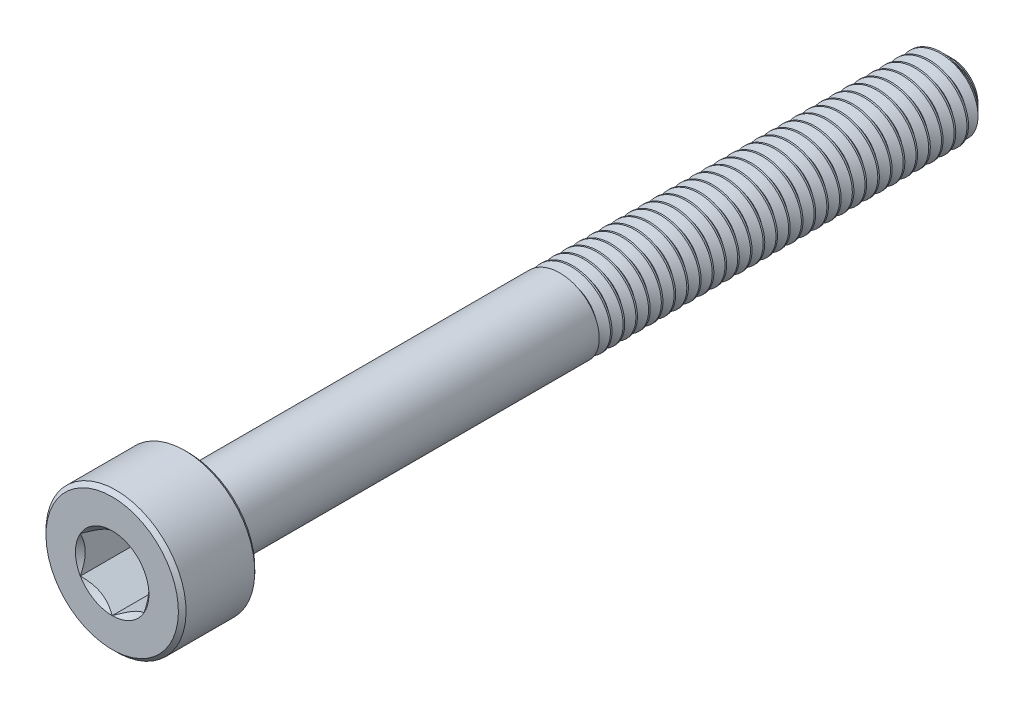
SolidWorks part; units mm, degrees
ref_plane "Front Plane" through (0, 0, 0) normal (0, 0, 1) x (1, 0, 0)
ref_plane "Top Plane" through (0, 0, 0) normal (0, 1, 0) x (1, 0, 0)
ref_plane "Right Plane" through (0, 0, 0) normal (1, 0, 0) x (0, 0, -1)
sketch "Sketch1" plane through (0, 0, 0) normal (1, 0, 0) x (0, 0, -1)
  line L0 (-16.5, 0) -> (16.5, 0) construction
  line L1 (16.5, 0) -> (16.5, 1) construction
  line L2 (16.5, 1) -> (16, 1.5) construction
  line L3 (16, 1.5) -> (16.125, 1.5) construction
  line L4 (16.125, 1.5) -> (-13.5, 1.5) construction
  line L5 (-13.5, 1.5) -> (-13.5, 2.75) construction
  line L6 (-13.5, 2.75) -> (-16.5, 2.75) construction
  line L7 (-16.5, 2.75) -> (-16.5, 0) construction
  line L8 (16.5, 1) -> (16.5, 1.5) construction
  line L9 (16.4687, 1.5541) -> (16.7187, 1.1211) construction
  line L10 (16.7187, 1.1211) -> (16.9687, 1.5541) construction
  line L11 (16.9687, 1.5541) -> (16.4687, 1.5541) construction
  line L12 (16.7187, 1.5541) -> (16.7187, 1.5) construction
  line L13 (16.7187, 1.1211) -> (16.7187, 1.1752) construction
  line L14 (16.6875, 1.1752) -> (16.75, 1.1752) construction
  line L15 (16.5, 1.5) -> (16.9375, 1.5) construction
  line L16 (16.4844, 1.5271) -> (16.9531, 1.5271) construction
  line L17 (16.5, 0) -> (16.5, -1.5) construction
  line L18 (-13.65, 2.75) -> (-13.5, 2.6) construction
  line L19 (-16.35, 2.75) -> (-16.5, 2.6) construction
  line L20 (-13.5, 1.5) -> (-13.5, 0) construction
  line L21 (-13.5, 0.75) -> (-3.5, 0.75) construction
  line L22 (-3.5, 0.75) -> (6.5, 0.75) construction
  line L23 (6.5, 0.75) -> (16.5, 0.75) construction
  line L24 (-3.5, 0.75) -> (-3.5, 1.5) construction
  line L25 (-3.5, 1.5) -> (-3.5, 2.75) construction
  line L26 (6.5, 0.75) -> (6.5, 2.75) construction
  point P0 (-16.5, 1.25)
  point P3 (15.25, 1.5)
  point P4 (0, 0)
  point P18 (6.5, 1.5)
  point P22 (16.7187, 1.1752)
  point P24 (16.125, 1.5)
  point P25 (16.7187, 1.5)
  point P28 (16.7187, 1.5271)
  point P29 (15.25, -1.5)
  point P30 (-3.5, 1.5)
  point P31 (-15, 2.75)
  point P37 (-14.025, 2.75)
  point P38 (-16.275, 2.75)
  point P45 (-3.5, 0.75)
  point P46 (6.5, 0.75)
  dimension "D1" = 45
  dimension "D2" = 0.0625
  dimension "D3" = 0.5
  dimension "D7" = 0.15
  dimension "D8" = 0.15
  dimension "D9" = 0.15
  dimension "D10" = 0.075
  dimension "D11" = 0.375
  dimension "Drive Size" = 2.5
  dimension "Head Diameter" = 5.5
  dimension "Head Height" = 3
  dimension "Thread Pitch" = 0.5
  dimension "Thread Major Diameter" = 3
  dimension "Length" = 30
  dimension "D12" = 0.375
  dimension "D4" = 1.25
sketch "Sketch2" plane through (0, 0, 0) normal (1, 0, 0) x (0, 0, -1)
  line L0 (-16.5, 0) -> (-16.5, 2.6)
  line L1 (-16.35, 2.75) -> (-13.65, 2.75)
  line L2 (-13.5, 2.6) -> (-13.5, 1.5)
  line L3 (-13.5, 1.5) -> (16, 1.5)
  line L4 (16, 1.5) -> (16.5, 1)
  line L5 (16.5, 1) -> (16.5, 0)
  line L6 (-13.65, 2.75) -> (-13.5, 2.6) construction
  line L7 (16.5, 0) -> (-16.5, 0)
  line L8 (-16.35, 2.75) -> (-16.5, 2.6) construction
  line L9 (-13.65, 2.75) -> (-13.5, 2.6)
  line L10 (-16.35, 2.75) -> (-16.5, 2.6)
revolve "Revolve1" add sketch "Sketch2" angle 360 about L7
sketch "Sketch3" plane through (0, 0, 16.5) normal (0, 0, 1) x (1, 0, 0)
  line L1 (1.25, -0.7217) -> (1.25, 0.7217)
  line L2 (1.25, 0.7217) -> (0, 1.4434)
  line L3 (0, 1.4434) -> (-1.25, 0.7217)
  line L4 (-1.25, 0.7217) -> (-1.25, -0.7217)
  line L5 (-1.25, -0.7217) -> (0, -1.4434)
  line L6 (0, -1.4434) -> (1.25, -0.7217)
  circle A0 centre (0, 0) radius 1.25 construction
extrude "Cut-Extrude1" cut sketch "Sketch3" against normal offset from surface (2 mm away) 1 up to face at (0, 2.6, 13.5)
sketch "Sketch4" plane through (0, 0, 16.5) normal (0, 0, 1) x (1, 0, 0)
  circle A0 centre (0, 0) radius 1.4434
extrude "Cut-Extrude2" cut sketch "Sketch4" against normal up to vertex (1.5 mm away) draft 45 up to point (0, 2.75, 15)
ref_plane "Plane1" through (0, 0, -16.125) normal (0, 0, 1) x (1, 0, 0)
split "Split1" bodies to split 106 resulting bodies 107 108 split by face at (0, 2.6, 13.5)
sketch "Sketch6" plane through (0, 0, -16.5) normal (0, 0, -1) x (-1, 0, 0)
  circle A0 centre (0, 0) radius 1.5
curve "Helix/Spiral1" pitch 0.5 height 15.575 radius 1.5 centre (0, 0, -16.5) axis (0, 0, 1) start towards (0, 1, 0)
sketch "Sketch7" plane through (0, 0, 0) normal (1, 0, 0) x (0, 0, -1)
  line L0 (16.4844, 1.5271) -> (16.9531, 1.5271)
  line L1 (16.9531, 1.5271) -> (16.75, 1.1752)
  line L2 (16.75, 1.1752) -> (16.6875, 1.1752)
  line L3 (16.6875, 1.1752) -> (16.4844, 1.5271)
sweep "Cut-Sweep1" cut profiles "Sketch7" path "Helix/Spiral1" align with end faces yes
sketch "Sketch8" plane through (0, 0, 13.5) normal (0, 0, -1) x (-1, 0, 0)
  circle A0 centre (0, 0) radius 1.5
extrude "Boss-Extrude1" add sketch "Sketch8" along normal through all draft 45
equation "\"D2@Sketch1\" = \"Thread Pitch@Sketch1\" / 8"
equation "\"D3@Sketch1\"= \"Thread Pitch@Sketch1\""
equation "\"D4@Helix/Spiral1\" = \"Thread Pitch@Sketch1\""
equation "\"D7@Sketch1\" = \"Head Height@Sketch1\" * .05"
equation "\"D8@Sketch1\"=\"D7@Sketch1\""
equation "\"D9@Sketch1\"=\"D7@Sketch1\""
equation "\"D10@Sketch1\"=\"D7@Sketch1\"/2"
equation "\"D11@Sketch1\"=\"D10@Sketch1\"*5"
equation "\"D4@Sketch1\"=\"Thread Pitch@Sketch1\"*2.5"
equation "\"D12@Sketch1\"=\"Thread Pitch@Sketch1\"*.75"
